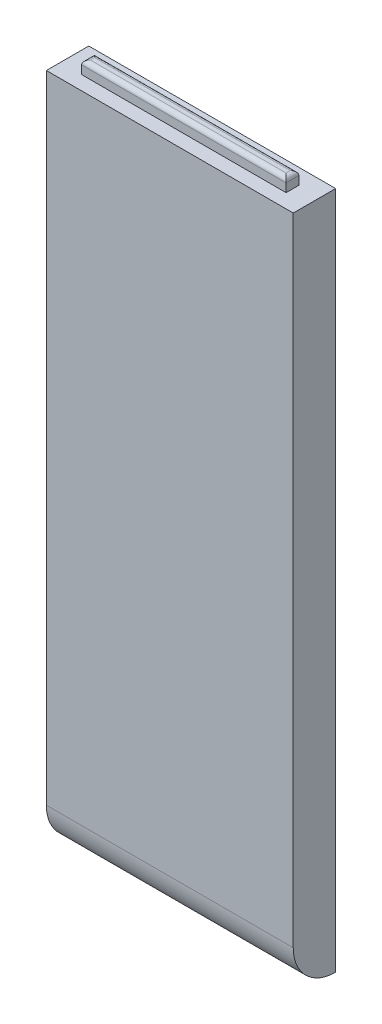
SolidWorks part; units mm, degrees
ref_plane "Front Plane" through (0, 0, 0) normal (0, 0, 1) x (1, 0, 0)
ref_plane "Top Plane" through (0, 0, 0) normal (0, 1, 0) x (1, 0, 0)
ref_plane "Right Plane" through (0, 0, 0) normal (1, 0, 0) x (0, 0, -1)
sketch "Sketch1" plane through (0, 0, 0) normal (0, 0, 1) x (1, 0, 0)
  line L1 (0, 0) -> (58.2, 0)
  line L2 (0, 0) -> (0, 160)
  line L3 (0, 160) -> (58.2, 160)
  line L4 (58.2, 0) -> (58.2, 160)
  dimension "D1" = 160
  dimension "D2" = 58.2
extrude "Boss-Extrude2" add sketch "Sketch1" along normal blind 10
fillet "Fillet2" radius 10 1 edges at (29.1, 0, 10)
sketch "Sketch2" plane through (0, 0, 0) normal (0, 0, -1) x (-1, 0, 0)
  line L0 (-58.2, 0) -> (-58.2, 160) construction
  line L1 (-53.2, 3.65) -> (-5, 3.65)
  line L2 (-53.2, 3.65) -> (-53.2, 1.35)
  line L3 (-53.2, 1.35) -> (-5, 1.35)
  line L4 (-5, 3.65) -> (-5, 1.35)
  line L5 (0, 160) -> (0, 0) construction
  line L6 (0, 0) -> (-58.2, 0) construction
  dimension "D1" = 5
  dimension "D2" = 5
  dimension "D3" = 1.35
  dimension "D4" = 2.3
extrude "Boss-Extrude3" add sketch "Sketch2" along normal blind 3
fillet "Fillet3" radius 1 4 edges at (5, 2.5, -3) (29.1, 1.35, -3) (53.2, 2.5, -3) (29.1, 3.65, -3)
sketch "Sketch4" plane through (0, 160, 0) normal (0, 1, 0) x (1, 0, 0)
  line L0 (0, -10) -> (0, 0) construction
  line L1 (5, -3.6809) -> (53.2, -3.6809)
  line L2 (5, -3.6809) -> (5, -6.6809)
  line L3 (5, -6.6809) -> (53.2, -6.6809)
  line L4 (53.2, -3.6809) -> (53.2, -6.6809)
  line L5 (58.2, -10) -> (58.2, 0) construction
  dimension "D1" = 3
  dimension "D2" = 5
  dimension "D3" = 5
extrude "Boss-Extrude4" add sketch "Sketch4" along normal blind 3
fillet "Fillet4" radius 1 4 edges at (53.2, 163, 5.1809) (29.1, 163, 3.6809) (5, 163, 5.1809) (29.1, 163, 6.6809)
